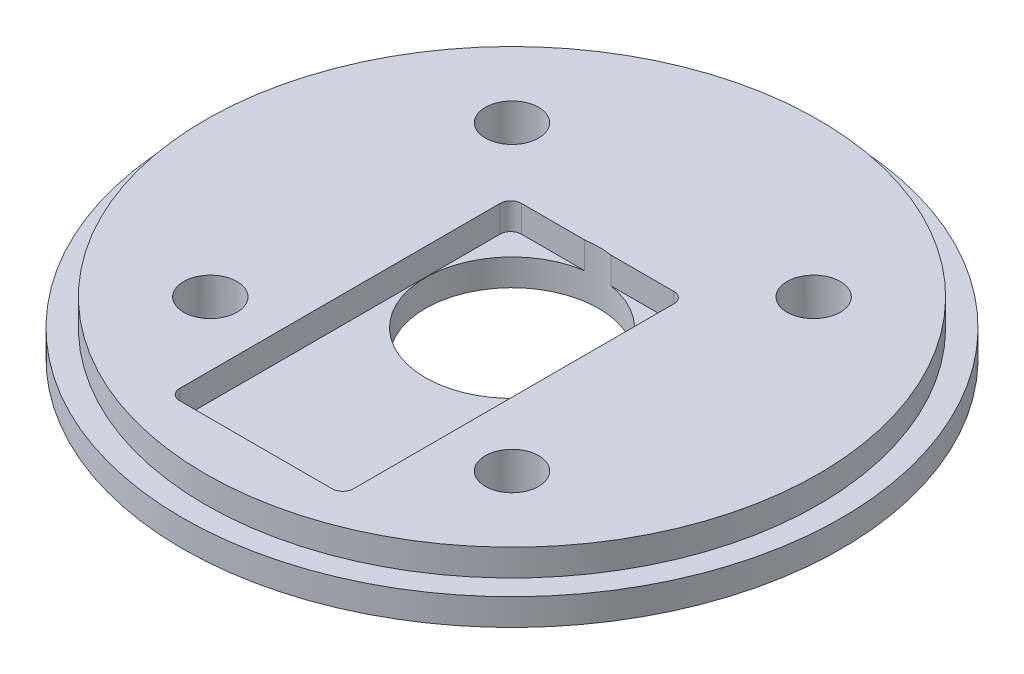
SolidWorks part; units mm, degrees
ref_plane "Front Plane" through (0, 0, 0) normal (0, 0, 1) x (1, 0, 0)
ref_plane "Top Plane" through (0, 0, 0) normal (0, 1, 0) x (1, 0, 0)
ref_plane "Right Plane" through (0, 0, 0) normal (1, 0, 0) x (0, 0, -1)
sketch "Sketch2" plane through (0, 0, 0) normal (0, 1, 0) x (1, 0, 0)
  circle A0 centre (0, 0) radius 39.243
  dimension "D1" = 78.486
extrude "Boss-Extrude1" add sketch "Sketch2" along normal blind 6.35
sketch "Sketch4" plane through (0, 6.35, 0) normal (0, 1, 0) x (1, 0, 0)
  circle A0 centre (0, 0) radius 36.5125
  circle A1 centre (0, 0) radius 39.243 construction
  circle A2 centre (0, 0) radius 39.243
  dimension "D1" = 73.025
extrude "Cut-Extrude1" cut sketch "Sketch4" against normal blind 3.175
sketch "Sketch5" plane through (0, 6.35, 0) normal (0, 1, 0) x (1, 0, 0)
  line L0 (17.9605, 17.9605) -> (-17.9605, -17.9605) construction
  line L1 (-17.9605, 17.9605) -> (17.9605, -17.9605) construction
  line L2 (-1000, 0) -> (49000, 0) construction
  point P1 (-17.9605, -17.9605)
  point P2 (17.9605, 17.9605)
  point P5 (17.9605, -17.9605)
  point P6 (-17.9605, 17.9605)
  dimension "D1" = 50.8
  dimension "D2" = 45
hole_wizard "1/4 (0.25) Diameter Hole1" positions "Sketch5" profile "Sketch6" hole size "1/4" standard "ANSI Inch" end condition through all
sketch "Sketch6" plane through (-17.9605, 6.35, -17.9605) normal (1, 0, 0) x (0, 0, 1)
  line L0 (0, 0) -> (0, 6.35)
  line L1 (0, 6.35) -> (3.175, 6.35)
  line L2 (3.175, 6.35) -> (3.175, 0)
  line L5 (3.175, 0) -> (0, 0)
  line L11 (0, -6.35) -> (0, 107.95) construction
  dimension "Thru Hole Dia." = 6.35
  dimension "Thru Hole Depth" = 6.35
sketch "Sketch7" plane through (0, 6.35, 0) normal (0, 1, 0) x (1, 0, 0)
  point P0 (0, 0)
hole_wizard "13/16 (0.8125) Diameter Hole1" positions "Sketch7" profile "Sketch8" hole size "13/16" standard "ANSI Inch" end condition through all
sketch "Sketch8" plane through (0, 6.35, 0) normal (1, 0, 0) x (0, 0, 1)
  line L0 (0, 0) -> (0, 6.35)
  line L1 (0, 6.35) -> (10.3187, 6.35)
  line L2 (10.3187, 6.35) -> (10.3187, 0)
  line L5 (10.3187, 0) -> (0, 0)
  line L11 (0, -6.35) -> (0, 107.95) construction
  dimension "Thru Hole Dia." = 20.6375
  dimension "Thru Hole Depth" = 6.35
sketch "Sketch9" plane through (0, 0, 0) normal (0, -1, 0) x (1, 0, 0)
  circle A0 centre (-17.9605, -17.9605) radius 3.175 construction
  circle A1 centre (17.9605, -17.9605) radius 3.175 construction
  circle A2 centre (17.9605, 17.9605) radius 3.175 construction
  circle A3 centre (-17.9605, 17.9605) radius 3.175 construction
  circle A4 centre (-17.9605, -17.9605) radius 3.175 construction
  circle A5 centre (17.9605, -17.9605) radius 3.175 construction
  circle A6 centre (17.9605, 17.9605) radius 3.175 construction
  circle A7 centre (-17.9605, 17.9605) radius 3.175 construction
  circle A8 centre (-17.9605, 17.9605) radius 6.35
  circle A9 centre (17.9605, 17.9605) radius 6.35
  circle A10 centre (17.9605, -17.9605) radius 6.35
  circle A11 centre (-17.9605, -17.9605) radius 6.35
  point P13 (-17.9605, 17.9605)
  point P14 (17.9605, 17.9605)
  point P15 (17.9605, -17.9605)
  point P16 (-17.9605, -17.9605)
  dimension "D1" = 12.7
extrude "Cut-Extrude2" cut sketch "Sketch9" against normal blind 1.5875
sketch "Sketch11" plane through (0, 6.35, 0) normal (0, 1, 0) x (1, 0, 0)
  line L1 (-10.35, 10.2) -> (10.35, 10.2)
  line L2 (-10.35, 10.2) -> (-10.35, -30.5)
  line L3 (-10.35, -30.5) -> (10.35, -30.5)
  line L4 (10.35, 10.2) -> (10.35, -30.5)
  line L5 (-10.35, 10.2) -> (10.35, -30.5) construction
  line L6 (-10.35, -30.5) -> (10.35, 10.2) construction
  point P0 (0, 0)
  point P1 (0, -10.15)
  dimension "D1" = 10.2
  dimension "D2" = 20.7
  dimension "D3" = 40.7
extrude "Cut-Extrude3" cut sketch "Sketch11" against normal blind 3.175
fillet "Fillet1" radius 1.27 4 edges at (-10.35, 4.7625, -10.2) (-10.35, 4.7625, 30.5) (10.35, 4.7625, 30.5) (10.35, 4.7625, -10.2)
equation "\"AIRFRAME_OD\"= 3.091in"
equation "\"AIRFRAME_ID\"= 3.00in"
equation "\"FLAT_T\"= 0.125in"
equation "\"NOSE_EXP_L\"= 3.5in"
equation "\"NOSE_SHOULDER_L\"= 5in"
equation "\"MAIN_L\"= 30in"
equation "\"RECO_COUP_L\"= 6in"
equation "\"RECO_SWITCH_L\"= 1.5in"
equation "\"DROGUE_L\"= 14in"
equation "\"ATS_FORE_COUP_L\"= 4in"
equation "\"ATS_AFT_COUP_L\"= 2.5in"
equation "\"LOWER_L\"= 16in"
equation "\"FIN_N\"= 4"
equation "\"CR_AFT_X\"= 0.5in"
equation "\"CR_FORE_X\"= 6in"
equation "\"D1@Boss-Extrude1\"=2*\"FLAT_T\""
equation "\"COUPLER_OD\"= 2.998in"
equation "\"COUPLER_ID\"= 2.875in"
equation "\"RECO_ROD_X\"= 1.5in"
equation "\"ATS_ROD_X\"= 2in"
equation "\"FIN_ROOT\"= 5in"
equation "\"FIN_X\"= 0.75in"
equation "\"MOTOR_OD\"= 2.25in"
equation "\"MOTOR_ID\"= 2.126in"
equation "\"MOTOR_L\"= 8in"
equation "\"MOTOR_LOWER_X\"= 0.5in"
equation "\"D1@Sketch4\"=\"COUPLER_ID\""
equation "\"D1@Cut-Extrude1\"=\"FLAT_T\""
equation "\"D1@Cut-Extrude3\"=\"FLAT_T\""
